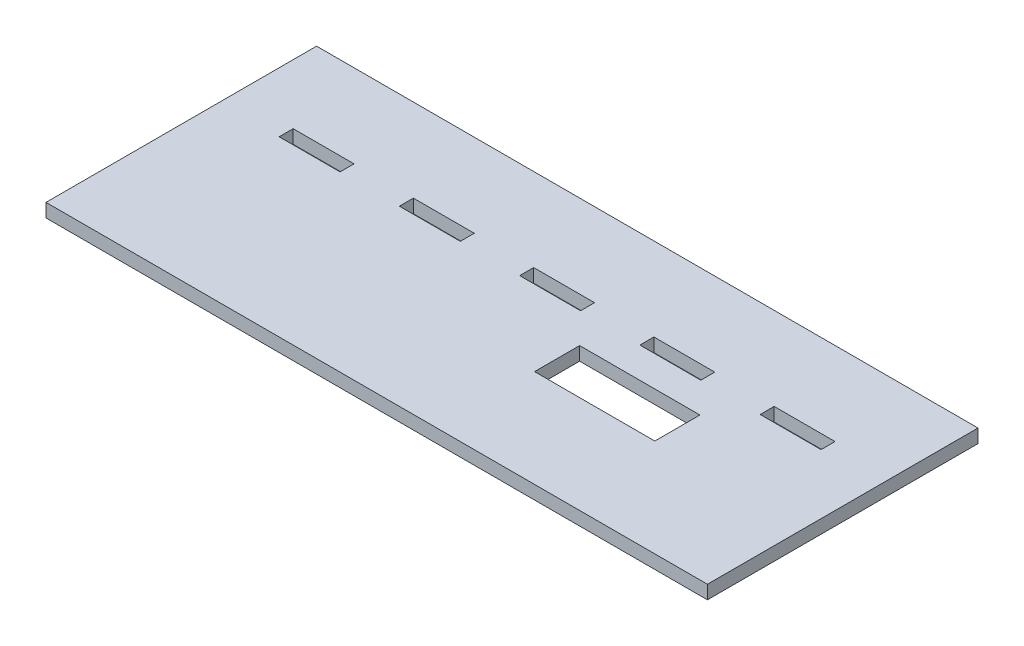
SolidWorks part; units mm, degrees
ref_plane "Front Plane" through (0, 0, 0) normal (0, 0, 1) x (1, 0, 0)
ref_plane "Top Plane" through (0, 0, 0) normal (0, 1, 0) x (1, 0, 0)
ref_plane "Right Plane" through (0, 0, 0) normal (1, 0, 0) x (0, 0, -1)
sketch "Sketch2" plane through (0, 0, 0) normal (0, 1, 0) x (1, 0, 0)
  line L3 (110, 45) -> (-110, 45)
  line L4 (110, 45) -> (110, -45)
  line L5 (110, -45) -> (-110, -45)
  line L6 (-110, 45) -> (-110, -45)
  line L7 (110, 45) -> (-110, -45) construction
  line L8 (110, -45) -> (-110, 45) construction
  point P0 (0, 0)
  dimension "D1" = 220
  dimension "D2" = 90
extrude "Boss-Extrude1" add sketch "Sketch2" along normal blind 4.5
sketch "Sketch3" plane through (0, 0, 0) normal (0, -1, 0) x (1, 0, 0)
  line L0 (0, 0) -> (0, -15) construction
  line L1 (50.125, -12.675) -> (50.125, -17.325)
  line L2 (10.125, -12.675) -> (-10.125, -12.675)
  line L3 (10.125, -12.675) -> (10.125, -17.325)
  line L4 (10.125, -17.325) -> (-10.125, -17.325)
  line L5 (-10.125, -12.675) -> (-10.125, -17.325)
  line L6 (10.125, -12.675) -> (-10.125, -17.325) construction
  line L7 (10.125, -17.325) -> (-10.125, -12.675) construction
  line L8 (50.125, -12.675) -> (29.875, -12.675)
  line L9 (29.875, -12.675) -> (29.875, -17.325)
  line L10 (50.125, -17.325) -> (29.875, -17.325)
  line L11 (90.125, -12.675) -> (90.125, -17.325)
  line L12 (90.125, -12.675) -> (69.875, -12.675)
  line L13 (69.875, -12.675) -> (69.875, -17.325)
  line L14 (90.125, -17.325) -> (69.875, -17.325)
  line L15 (10.125, -12.675) -> (50.125, -12.675) construction
  line L16 (-90.125, -17.325) -> (-69.875, -17.325)
  line L17 (-69.875, -12.675) -> (-69.875, -17.325)
  line L18 (-90.125, -12.675) -> (-69.875, -12.675)
  line L19 (-90.125, -12.675) -> (-90.125, -17.325)
  line L20 (-50.125, -17.325) -> (-29.875, -17.325)
  line L21 (-29.875, -12.675) -> (-29.875, -17.325)
  line L22 (-50.125, -12.675) -> (-29.875, -12.675)
  line L23 (-50.125, -12.675) -> (-50.125, -17.325)
  dimension "D1" = 15
  dimension "D2" = 20.25
  dimension "D3" = 4.65
  dimension "D5" = 40
  dimension "D4" = 3
extrude "Cut-Extrude1" cut sketch "Sketch3" against normal through all
sketch "Sketch4" plane through (0, 0, 0) normal (0, -1, 0) x (1, 0, 0)
  line L0 (0, 5) -> (40, 5) construction
  line L1 (0, 0) -> (0, 5) construction
  line L2 (60, 12.5) -> (20, 12.5)
  line L3 (60, 12.5) -> (60, -2.5)
  line L4 (60, -2.5) -> (20, -2.5)
  line L5 (20, 12.5) -> (20, -2.5)
  line L6 (60, 12.5) -> (20, -2.5) construction
  line L7 (60, -2.5) -> (20, 12.5) construction
  dimension "D1" = 40
  dimension "D2" = 15
  dimension "D3" = 5
  dimension "D4" = 40
extrude "Input link cut" cut sketch "Sketch4" against normal through all
